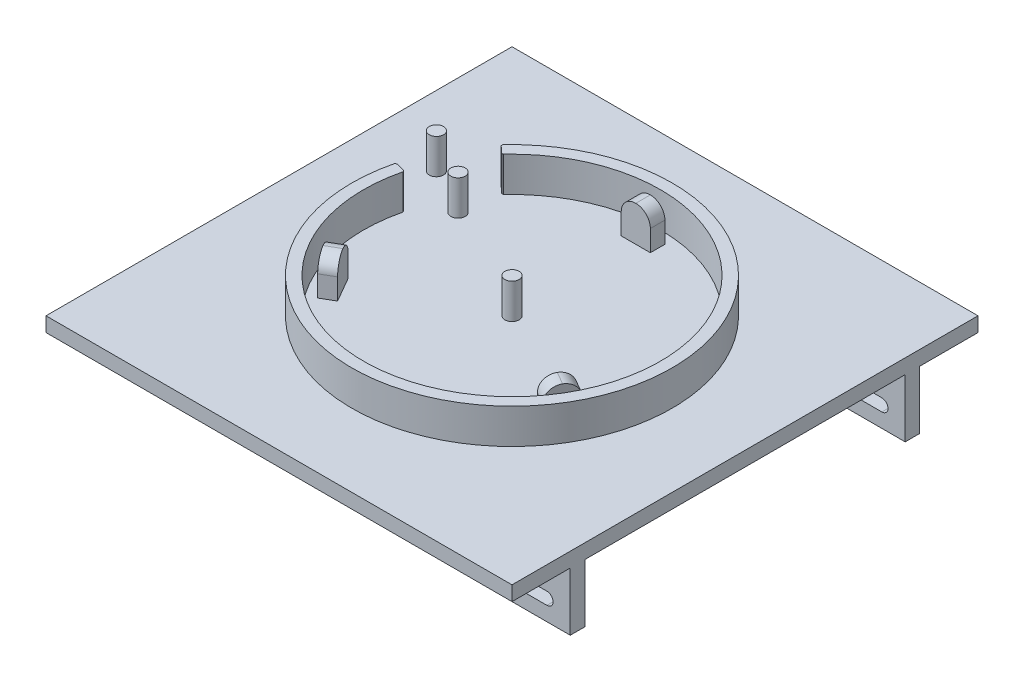
SolidWorks part; units mm, degrees
ref_plane "Vorne" through (0, 0, 0) normal (0, 0, 1) x (1, 0, 0)
ref_plane "Oben" through (0, 0, 0) normal (0, 1, 0) x (1, 0, 0)
ref_plane "Seite" through (0, 0, 0) normal (1, 0, 0) x (0, 0, -1)
sketch "Skizze1" plane through (0, 0, 0) normal (0, 1, 0) x (1, 0, 0)
  line L1 (80, -80) -> (-80, -80)
  line L2 (80, -80) -> (80, 80)
  line L3 (80, 80) -> (-80, 80)
  line L4 (-80, -80) -> (-80, 80)
  line L5 (80, -80) -> (-80, 80) construction
  line L6 (80, 80) -> (-80, -80) construction
  point P0 (0, 0)
  dimension "D1" = 160
extrude "Aufsatz-Linear austragen1" add sketch "Skizze1" along normal blind 5
sketch "Skizze2" plane through (0, 0, 0) normal (0, -1, 0) x (-1, 0, 0)
  line L0 (-80, 0) -> (80, 0) construction
  line L5 (80, -57.5) -> (-80, -57.5) construction
  line L6 (80, 55) -> (-80, 55)
  line L7 (80, 55) -> (80, 60)
  line L8 (80, 60) -> (-80, 60)
  line L9 (-80, 55) -> (-80, 60)
  line L10 (0, 60) -> (0, 55) construction
  line L15 (-80, -80) -> (-80, 80) construction
  line L16 (80, 80) -> (80, -80) construction
  line L17 (0, -80) -> (0, 80) construction
  line L18 (80, -80) -> (-80, -80) construction
  line L19 (-80, 80) -> (80, 80) construction
  line L20 (80, 57.5) -> (-80, 57.5) construction
  line L21 (0, -60) -> (0, -55) construction
  line L22 (-80, -55) -> (-80, -60)
  line L23 (80, -60) -> (-80, -60)
  line L24 (80, -55) -> (80, -60)
  line L25 (80, -55) -> (-80, -55)
  point P28 (0, -57.5)
  point P672 (0, 57.5)
  dimension "D1" = 160
  dimension "D2" = 5
  dimension "D3" = 60
extrude "Aufsatz-Linear austragen2" add sketch "Skizze2" along normal blind 20
sketch "Skizze3" plane through (0, 0, 0) normal (0, 0, 1) x (1, 0, 0)
  line L0 (25, -10.9) -> (72, -10.9)
  line L1 (25, -15.1) -> (72, -15.1)
  line L2 (80, -20) -> (-80, -20) construction
  line L3 (80, -20) -> (80, 0) construction
  line L4 (-80, -20) -> (-80, 0) construction
  line L5 (-3.7, -20) -> (3.7, -20)
  circle A0 centre (-72, -13) radius 2.1
  arc A1 (72, -15.1) -> (72, -10.9) centre (72, -13) ccw
  arc A2 (25, -10.9) -> (25, -15.1) centre (25, -13) ccw
  arc A3 (3.7, -20) -> (-3.7, -20) centre (0, -20) ccw
  dimension "D2" = 4.2
  dimension "D6" = 3.7
  dimension "D1" = 7
  dimension "D3" = 47
  dimension "D4" = 8
  dimension "D5" = 8
extrude "Schnitt-Linear austragen1" cut sketch "Skizze3" against normal through all both and the other way through all
sketch "Skizze4" plane through (0, 5, 0) normal (0, 1, 0) x (1, 0, 0)
  line L0 (-49.4361, 12.5326) -> (-53.3135, 13.5156)
  line L1 (-80, 80) -> (-80, -80) construction
  line L2 (-37.7606, 34.2803) -> (-40.7222, 36.9689)
  line L3 (-49.4361, 12.5326) -> (-40, 21.4746) construction
  line L4 (-40, 21.4746) -> (-37.7606, 34.2803) construction
  line L5 (0, 0) -> (-40, 21.4746) construction
  line L6 (-40, 21.4746) -> (-80, 42.9493) construction
  circle A0 centre (0, 0) radius 2.45
  circle A3 centre (-40, 21.4746) radius 2.45
  arc A4 (-53.3135, 13.5156) -> (-40.7222, 36.9689) centre (0, 0) ccw
  arc A5 (-49.4361, 12.5326) -> (-37.7606, 34.2803) centre (0, 0) ccw
  circle A6 centre (-56.0352, 30.0834) radius 2.45
  dimension "D1" = 4.9
  dimension "D4" = 18.2
  dimension "D6" = 13
  dimension "D3" = 40
  dimension "55" = 55
  dimension "D5" = 51
  dimension "D2" = 45.4
extrude "Aufsatz-Linear austragen3" add sketch "Skizze4" along normal blind 12
chamfer "Fase1" distance 0.4 angle 45 4 edges at (-49.4361, 11, -12.5326) (-53.3135, 11, -13.5156) (-40.7222, 11, -36.9689) (-37.7606, 11, -34.2803)
sketch "Skizze6" plane through (0, 5, 0) normal (0, 1, 0) x (1, 0, 0)
  line L0 (0, 45) -> (-38.9711, -22.5) construction
  line L1 (-38.9711, -22.5) -> (38.9711, -22.5) construction
  line L2 (38.9711, -22.5) -> (0, 45) construction
  line L3 (0, 0) -> (-38.9711, -22.5) construction
  line L4 (0, 0) -> (38.9711, -22.5) construction
  line L5 (0, 0) -> (0, 45) construction
  line L6 (43.6362, -19.4199) -> (39.3061, -16.9199)
  line L7 (39.3061, -16.9199) -> (34.3061, -25.5801)
  line L8 (34.3061, -25.5801) -> (38.6362, -28.0801)
  line L9 (38.6362, -28.0801) -> (43.6362, -19.4199)
  line L10 (-34.3061, -25.5801) -> (-39.3061, -16.9199)
  line L11 (-39.3061, -16.9199) -> (-43.6362, -19.4199)
  line L12 (-43.6362, -19.4199) -> (-38.6362, -28.0801)
  line L13 (-38.6362, -28.0801) -> (-34.3061, -25.5801)
  line L14 (5, 42.5) -> (-5, 42.5)
  line L15 (-5, 42.5) -> (-5, 47.5)
  line L16 (-5, 47.5) -> (5, 47.5)
  line L17 (5, 47.5) -> (5, 42.5)
  line L18 (5, 47.5) -> (-5, 42.5) construction
  line L19 (-5, 47.5) -> (5, 42.5) construction
  line L20 (39.3061, -16.9199) -> (38.6362, -28.0801) construction
  line L21 (34.3061, -25.5801) -> (43.6362, -19.4199) construction
  line L22 (-38.6362, -28.0801) -> (-39.3061, -16.9199) construction
  line L23 (-43.6362, -19.4199) -> (-34.3061, -25.5801) construction
  circle A0 centre (0, 0) radius 45 construction
  point P3 (-38.9711, -22.5)
  point P4 (0, 45)
  point P5 (38.9711, -22.5)
  point P19 (0, 45)
  point P22 (38.9711, -22.5)
  point P23 (-38.9711, -22.5)
  dimension "D1" = 90
  dimension "D2" = 10
  dimension "D3" = 5
extrude "Aufsatz-Linear austragen4" add sketch "Skizze6" along normal blind 12.2 separate body
fillet "Verrundung1" radius 5 2 edges at (36.4711, 17.2, 26.8301) (41.4711, 17.2, 18.1699)
fillet "Verrundung2" radius 5 2 edges at (-36.4711, 17.2, 26.8301) (-41.4711, 17.2, 18.1699)
fillet "Verrundung3" radius 5 2 edges at (-5, 17.2, -45) (5, 17.2, -45)
